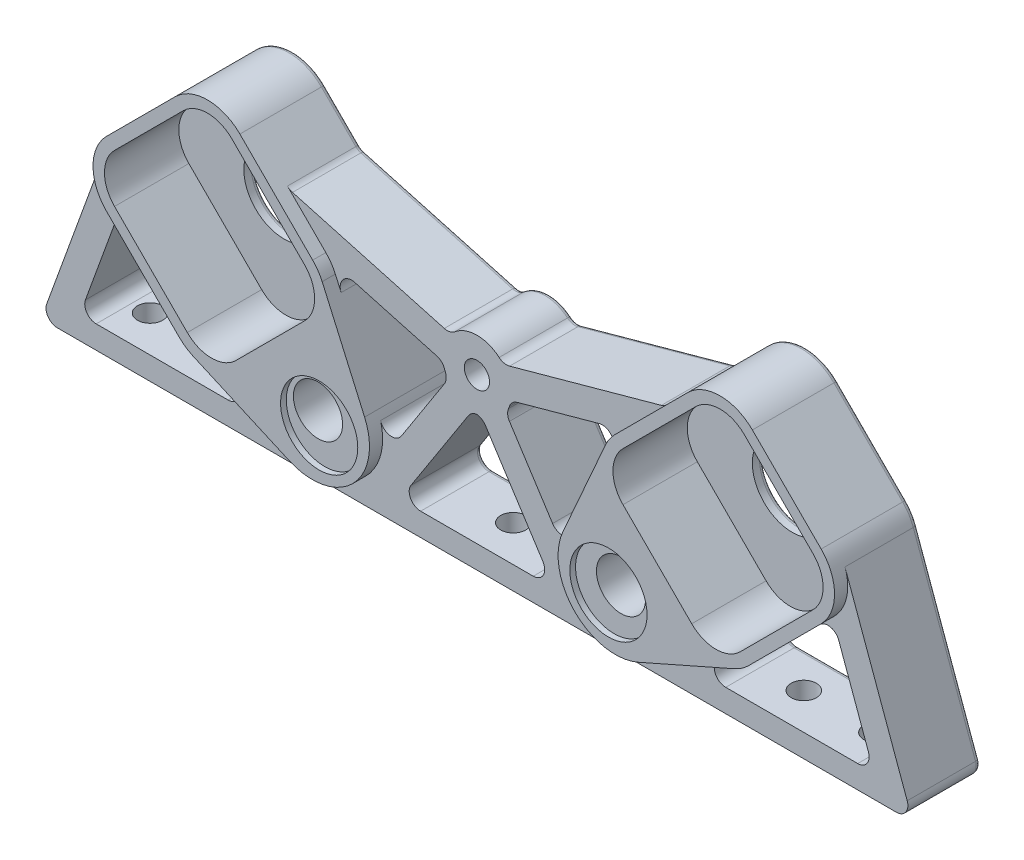
SolidWorks part; units mm, degrees
ref_plane "Front Plane" through (0, 0, 0) normal (0, 0, 1) x (1, 0, 0)
ref_plane "Top Plane" through (0, 0, 0) normal (0, 1, 0) x (1, 0, 0)
ref_plane "Right Plane" through (0, 0, 0) normal (1, 0, 0) x (0, 0, -1)
sketch "Sketch1" plane through (0, 0, 0) normal (0, 0, 1) x (1, 0, 0)
  line L0 (0, 0) -> (60.4965, 0) construction
  circle A0 centre (0, 0) radius 25.4 construction
  circle A1 centre (44.45, 35.921) radius 31.75 construction
  circle A2 centre (133.35, 35.921) radius 31.75 construction
  circle A3 centre (177.8, 0) radius 25.4 construction
  circle A4 centre (222.25, 35.921) radius 31.75 construction
  circle A5 centre (311.15, 35.921) radius 31.75 construction
  circle A6 centre (355.6, 0) radius 25.4 construction
  circle A7 centre (0, 0) radius 50.8 construction
  circle A8 centre (355.6, 0) radius 50.8 construction
  circle A9 centre (177.8, 0) radius 50.8 construction
  circle A10 centre (88.9, 35.921) radius 12.7 construction
  circle A11 centre (266.7, 35.921) radius 12.7 construction
  point P20 (-50.8, 0)
  point P21 (406.4, 0)
  dimension "D1" = 50.8
  dimension "D2" = 63.5
  dimension "D4" = 101.6
  dimension "D5" = 25.4
  dimension "D6" = 25.4
  dimension "D3" = 355.6
  dimension "D7" = 177.8
  dimension "D8" = 177.8
  dimension "D9" = 457.2
  dimension "D10" = 44.45
sketch "Sketch2" plane through (0, 0, 0) normal (0, 0, 1) x (1, 0, 0)
  line L0 (-200000, 0) -> (200060.4965, 0) construction
  line L1 (-44.45, 6.35) -> (400.05, 6.35) construction
  line L2 (-44.45, 6.35) -> (-44.45, -19.05) construction
  line L3 (-44.45, -19.05) -> (400.05, -19.05) construction
  line L4 (400.05, 6.35) -> (400.05, -19.05) construction
  circle A0 centre (-38.1, 0) radius 2.25 construction
  circle A2 centre (-31.75, -6.35) radius 2.25 construction
  circle A3 centre (-25.4, 0) radius 2.25 construction
  circle A4 centre (-12.7, 0) radius 2.25 construction
  circle A5 centre (0, 0) radius 2.25 construction
  circle A6 centre (12.7, 0) radius 2.25 construction
  circle A7 centre (25.4, 0) radius 2.25 construction
  circle A8 centre (38.1, 0) radius 2.25 construction
  circle A9 centre (50.8, 0) radius 2.25 construction
  circle A10 centre (63.5, 0) radius 2.25 construction
  circle A11 centre (76.2, 0) radius 2.25 construction
  circle A12 centre (88.9, 0) radius 2.25 construction
  circle A13 centre (101.6, 0) radius 2.25 construction
  circle A14 centre (114.3, 0) radius 2.25 construction
  circle A15 centre (127, 0) radius 2.25 construction
  circle A16 centre (139.7, 0) radius 2.25 construction
  circle A17 centre (152.4, 0) radius 2.25 construction
  circle A18 centre (165.1, 0) radius 2.25 construction
  circle A19 centre (177.8, 0) radius 2.25 construction
  circle A20 centre (190.5, 0) radius 2.25 construction
  circle A21 centre (203.2, 0) radius 2.25 construction
  circle A22 centre (215.9, 0) radius 2.25 construction
  circle A23 centre (228.6, 0) radius 2.25 construction
  circle A24 centre (241.3, 0) radius 2.25 construction
  circle A25 centre (254, 0) radius 2.25 construction
  circle A26 centre (266.7, 0) radius 2.25 construction
  circle A27 centre (279.4, 0) radius 2.25 construction
  circle A28 centre (292.1, 0) radius 2.25 construction
  circle A29 centre (304.8, 0) radius 2.25 construction
  circle A30 centre (317.5, 0) radius 2.25 construction
  circle A31 centre (330.2, 0) radius 2.25 construction
  circle A32 centre (342.9, 0) radius 2.25 construction
  circle A33 centre (355.6, 0) radius 2.25 construction
  circle A34 centre (368.3, 0) radius 2.25 construction
  circle A35 centre (381, 0) radius 2.25 construction
  circle A36 centre (393.7, 0) radius 2.25 construction
  circle A37 centre (-25.4, -12.7) radius 2.25 construction
  circle A38 centre (-12.7, -12.7) radius 2.25 construction
  circle A39 centre (0, -12.7) radius 2.25 construction
  circle A40 centre (12.7, -12.7) radius 2.25 construction
  circle A41 centre (25.4, -12.7) radius 2.25 construction
  circle A42 centre (38.1, -12.7) radius 2.25 construction
  circle A43 centre (50.8, -12.7) radius 2.25 construction
  circle A44 centre (63.5, -12.7) radius 2.25 construction
  circle A45 centre (76.2, -12.7) radius 2.25 construction
  circle A46 centre (88.9, -12.7) radius 2.25 construction
  circle A47 centre (101.6, -12.7) radius 2.25 construction
  circle A48 centre (114.3, -12.7) radius 2.25 construction
  circle A49 centre (127, -12.7) radius 2.25 construction
  circle A50 centre (139.7, -12.7) radius 2.25 construction
  circle A51 centre (152.4, -12.7) radius 2.25 construction
  circle A52 centre (165.1, -12.7) radius 2.25 construction
  circle A53 centre (177.8, -12.7) radius 2.25 construction
  circle A54 centre (190.5, -12.7) radius 2.25 construction
  circle A55 centre (203.2, -12.7) radius 2.25 construction
  circle A56 centre (215.9, -12.7) radius 2.25 construction
  circle A57 centre (228.6, -12.7) radius 2.25 construction
  circle A58 centre (241.3, -12.7) radius 2.25 construction
  circle A59 centre (254, -12.7) radius 2.25 construction
  circle A60 centre (266.7, -12.7) radius 2.25 construction
  circle A61 centre (279.4, -12.7) radius 2.25 construction
  circle A62 centre (292.1, -12.7) radius 2.25 construction
  circle A63 centre (304.8, -12.7) radius 2.25 construction
  circle A64 centre (317.5, -12.7) radius 2.25 construction
  circle A65 centre (330.2, -12.7) radius 2.25 construction
  circle A66 centre (342.9, -12.7) radius 2.25 construction
  circle A67 centre (355.6, -12.7) radius 2.25 construction
  circle A68 centre (368.3, -12.7) radius 2.25 construction
  circle A69 centre (381, -12.7) radius 2.25 construction
  circle A70 centre (393.7, -12.7) radius 2.25 construction
  circle A71 centre (-38.1, -12.7) radius 2.25 construction
  circle A72 centre (-19.05, -6.35) radius 2.25 construction
  circle A73 centre (-6.35, -6.35) radius 2.25 construction
  circle A74 centre (6.35, -6.35) radius 2.25 construction
  circle A75 centre (19.05, -6.35) radius 2.25 construction
  circle A76 centre (31.75, -6.35) radius 2.25 construction
  circle A77 centre (44.45, -6.35) radius 2.25 construction
  circle A78 centre (57.15, -6.35) radius 2.25 construction
  circle A79 centre (69.85, -6.35) radius 2.25 construction
  circle A80 centre (82.55, -6.35) radius 2.25 construction
  circle A81 centre (95.25, -6.35) radius 2.25 construction
  circle A82 centre (107.95, -6.35) radius 2.25 construction
  circle A83 centre (120.65, -6.35) radius 2.25 construction
  circle A84 centre (133.35, -6.35) radius 2.25 construction
  circle A85 centre (146.05, -6.35) radius 2.25 construction
  circle A86 centre (158.75, -6.35) radius 2.25 construction
  circle A87 centre (171.45, -6.35) radius 2.25 construction
  circle A88 centre (184.15, -6.35) radius 2.25 construction
  circle A89 centre (196.85, -6.35) radius 2.25 construction
  circle A90 centre (209.55, -6.35) radius 2.25 construction
  circle A91 centre (222.25, -6.35) radius 2.25 construction
  circle A92 centre (234.95, -6.35) radius 2.25 construction
  circle A93 centre (247.65, -6.35) radius 2.25 construction
  circle A94 centre (260.35, -6.35) radius 2.25 construction
  circle A95 centre (273.05, -6.35) radius 2.25 construction
  circle A96 centre (285.75, -6.35) radius 2.25 construction
  circle A97 centre (298.45, -6.35) radius 2.25 construction
  circle A98 centre (311.15, -6.35) radius 2.25 construction
  circle A99 centre (323.85, -6.35) radius 2.25 construction
  circle A100 centre (336.55, -6.35) radius 2.25 construction
  circle A101 centre (349.25, -6.35) radius 2.25 construction
  circle A102 centre (361.95, -6.35) radius 2.25 construction
  circle A103 centre (374.65, -6.35) radius 2.25 construction
  circle A104 centre (387.35, -6.35) radius 2.25 construction
  point P4 (0, 0)
  point P7 (0, 0)
  dimension "D5" = 4.5
  dimension "D1" = 25.4
  dimension "D2" = 444.5
  dimension "D3" = 6.35
  dimension "D4" = 44.45
  dimension "D6" = 6.35
  dimension "D7" = 6.35
  dimension "D8" = 6.35
  dimension "D12" = 12.7
  dimension "D9" = 35
  dimension "D10" = 2
  dimension "D11" = 34
sketch "Sketch4" plane through (0, 0, 0) normal (0, 0, 1) x (1, 0, 0)
  line L0 (61.067, 39.8101) -> (48.3391, 52.538)
  line L1 (61.067, 31.3248) -> (49.0462, 19.304)
  line L2 (39.8538, 52.538) -> (27.833, 40.5172)
  line L3 (40.5609, 19.304) -> (27.833, 32.0319)
  line L4 (65.3097, 35.5675) -> (23.5903, 36.2746) construction
  line L5 (44.0964, 56.7807) -> (44.8036, 15.0614) construction
  line L6 (44.9803, 59.0788) -> (21.2923, 35.3907) construction
  line L7 (44.45, 35.921) -> (62.4105, 17.9605) construction
  line L8 (62.4105, 17.9605) -> (63.6126, 16.7584) construction
  line L9 (33.1363, 47.2347) -> (74.1485, 6.2225) construction
  line L10 (88.9, 35.921) -> (88.9, 9.7206) construction
  line L11 (44.9803, 59.0788) -> (85.9925, 18.0666) construction
  line L12 (21.2923, 35.3907) -> (62.3044, -5.6215) construction
  line L13 (85.9925, 18.0666) -> (62.3044, -5.6215) construction
  line L14 (132.8197, 59.0788) -> (156.5077, 35.3907) construction
  line L15 (156.5077, 35.3907) -> (115.4956, -5.6215) construction
  line L16 (132.8197, 59.0788) -> (91.8075, 18.0666) construction
  line L17 (91.8075, 18.0666) -> (115.4956, -5.6215) construction
  line L18 (137.9462, 52.538) -> (149.967, 40.5172)
  line L19 (137.2391, 19.304) -> (149.967, 32.0319)
  line L20 (116.733, 31.3248) -> (128.7538, 19.304)
  line L21 (116.733, 39.8101) -> (129.4609, 52.538)
  line L25 (-44.45, 6.35) -> (400.05, 6.35) construction
  circle A0 centre (44.45, 35.921) radius 7
  circle A1 centre (88.9, 35.921) radius 2.2
  arc A3 (61.067, 39.8101) -> (61.067, 31.3248) centre (56.8244, 35.5675) cw
  circle A4 centre (62.4105, 17.9605) radius 4.3
  circle A5 centre (63.6126, 16.7584) radius 6.75
  arc A6 (49.0462, 19.304) -> (40.5609, 19.304) centre (44.8036, 23.5467) cw
  arc A7 (27.833, 32.0319) -> (27.833, 40.5172) centre (32.0756, 36.2746) cw
  arc A8 (39.8538, 52.538) -> (48.3391, 52.538) centre (44.0964, 48.2954) cw
  circle A9 centre (115.3895, 17.9605) radius 4.3
  circle A10 centre (114.1874, 16.7584) radius 6.75
  circle A11 centre (133.35, 35.921) radius 7
  arc A12 (149.967, 32.0319) -> (149.967, 40.5172) centre (145.7244, 36.2746) ccw
  arc A13 (128.7538, 19.304) -> (137.2391, 19.304) centre (132.9964, 23.5467) ccw
  arc A14 (116.733, 39.8101) -> (116.733, 31.3248) centre (120.9756, 35.5675) ccw
  arc A15 (137.9462, 52.538) -> (129.4609, 52.538) centre (133.7036, 48.2954) ccw
  dimension "D1" = 4.4
  dimension "D2" = 14
  dimension "D7" = 13.5
  dimension "D8" = 8.6
  dimension "D9" = 6
  dimension "D3" = 29
  dimension "D4" = 30
  dimension "D5" = 10.4
  dimension "D6" = 1.7
  dimension "D10" = 58
  dimension "D11" = 33.5
  dimension "D12" = 16
  dimension "D13" = 45
sketch "Sketch6" plane through (0, 0, 0) normal (0, 0, 1) x (1, 0, 0)
  line L0 (72.4105, 10.35) -> (105.3895, 10.35)
  line L1 (88.9, 200035.921) -> (88.9, -199990.2794) construction
  line L2 (165.1, 6.35) -> (12.7, 6.35)
  line L3 (-44.45, 6.35) -> (400.05, 6.35) construction
  line L8 (40.5609, 19.304) -> (27.833, 32.0319) construction
  line L9 (61.067, 31.3248) -> (49.0462, 19.304) construction
  line L10 (61.067, 39.8101) -> (48.3391, 52.538) construction
  line L11 (39.8538, 52.538) -> (27.833, 40.5172) construction
  line L12 (40.5609, 19.304) -> (27.833, 32.0319) construction
  line L13 (61.067, 31.3248) -> (49.0462, 19.304) construction
  line L14 (61.067, 39.8101) -> (48.3391, 52.538) construction
  line L15 (62.4812, 41.2243) -> (49.7533, 53.9522)
  line L16 (39.8538, 52.538) -> (27.833, 40.5172) construction
  line L18 (38.4396, 53.9522) -> (26.4188, 41.9314)
  line L21 (39.1467, 17.8898) -> (26.4188, 30.6177)
  line L22 (71.5588, 21.9989) -> (64.143, 38.7982)
  line L23 (41.5728, 16.228) -> (58.3721, 8.8122)
  line L24 (54.8885, 10.35) -> (19.4716, 10.35)
  line L34 (19.4716, 10.35) -> (26.7206, 30.3159)
  line L37 (88.9, 35.921) -> (105.3895, 10.35) construction
  line L38 (12.7, 6.35) -> (24.5559, 39.0048)
  line L39 (88.9, 35.921) -> (44.0964, 48.2954) construction
  line L40 (84.308, 39.7829) -> (56.144, 47.5616)
  line L41 (63.1751, 40.4324) -> (82.9769, 34.9633)
  line L42 (88.9, 35.921) -> (133.7036, 48.2954) construction
  line L43 (137.9462, 52.538) -> (149.967, 40.5172) construction
  line L44 (88.9, 35.921) -> (72.4105, 10.35) construction
  line L45 (116.733, 39.8101) -> (129.4609, 52.538) construction
  line L46 (72.4105, 17.9605) -> (72.4105, 10.35)
  line L47 (72.4105, 14.963) -> (83.843, 32.692)
  line L48 (75.3852, 10.35) -> (88.0451, 29.9822)
  line L49 (116.733, 31.3248) -> (128.7538, 19.304) construction
  line L50 (88.9, 35.921) -> (88.9, 10.35) construction
  line L51 (137.2391, 19.304) -> (149.967, 32.0319) construction
  line L52 (102.4148, 10.35) -> (89.7549, 29.9822)
  line L53 (105.3895, 14.963) -> (93.957, 32.692)
  line L54 (105.3895, 17.9605) -> (105.3895, 10.35)
  line L55 (114.6249, 40.4324) -> (94.8231, 34.9633)
  line L56 (93.492, 39.7829) -> (121.656, 47.5616)
  line L57 (165.1, 6.35) -> (153.2441, 39.0048)
  line L58 (158.3284, 10.35) -> (151.0794, 30.3159)
  line L59 (122.9115, 10.35) -> (158.3284, 10.35)
  line L60 (136.2272, 16.228) -> (119.4279, 8.8122)
  line L61 (106.2412, 21.9989) -> (113.657, 38.7982)
  line L62 (138.6533, 17.8898) -> (151.3812, 30.6177)
  line L63 (139.3604, 53.9522) -> (151.3812, 41.9314)
  line L64 (115.3188, 41.2243) -> (128.0467, 53.9522)
  arc A0 (62.4812, 29.9106) -> (62.4812, 41.2243) centre (56.8244, 35.5675) ccw
  arc A1 (39.1467, 17.8898) -> (50.4604, 17.8898) centre (44.8036, 23.5467) ccw
  arc A2 (149.967, 40.5172) -> (149.967, 32.0319) centre (145.7244, 36.2746) cw construction
  arc A3 (129.4609, 52.538) -> (137.9462, 52.538) centre (133.7036, 48.2954) cw construction
  arc A4 (116.733, 31.3248) -> (116.733, 39.8101) centre (120.9756, 35.5675) cw construction
  arc A5 (137.2391, 19.304) -> (128.7538, 19.304) centre (132.9964, 23.5467) cw construction
  arc A12 (40.5609, 19.304) -> (49.0462, 19.304) centre (44.8036, 23.5467) ccw construction
  arc A14 (61.067, 31.3248) -> (61.067, 39.8101) centre (56.8244, 35.5675) ccw construction
  arc A15 (48.3391, 52.538) -> (39.8538, 52.538) centre (44.0964, 48.2954) ccw construction
  arc A16 (27.833, 40.5172) -> (27.833, 32.0319) centre (32.0756, 36.2746) ccw construction
  arc A17 (40.5609, 19.304) -> (49.0462, 19.304) centre (44.8036, 23.5467) ccw construction
  arc A18 (61.067, 31.3248) -> (61.067, 39.8101) centre (56.8244, 35.5675) ccw construction
  arc A19 (48.3391, 52.538) -> (39.8538, 52.538) centre (44.0964, 48.2954) ccw construction
  arc A20 (27.833, 40.5172) -> (27.833, 32.0319) centre (32.0756, 36.2746) ccw construction
  arc A21 (26.4188, 41.9314) -> (26.4188, 30.6177) centre (32.0756, 36.2746) ccw
  arc A22 (49.7533, 53.9522) -> (38.4396, 53.9522) centre (44.0964, 48.2954) ccw
  circle A25 centre (62.4105, 17.9605) radius 4.3 construction
  circle A26 centre (62.4105, 17.9605) radius 4.3
  circle A27 centre (115.3895, 17.9605) radius 10
  circle A28 centre (115.3895, 17.9605) radius 4.3
  arc A29 (128.0467, 53.9522) -> (139.3604, 53.9522) centre (133.7036, 48.2954) cw
  arc A30 (151.3812, 41.9314) -> (151.3812, 30.6177) centre (145.7244, 36.2746) cw
  arc A41 (138.6533, 17.8898) -> (127.3396, 17.8898) centre (132.9964, 23.5467) cw
  arc A42 (115.3188, 29.9106) -> (115.3188, 41.2243) centre (120.9756, 35.5675) cw
  circle A43 centre (62.4105, 17.9605) radius 10
  circle A44 centre (88.9, 35.921) radius 6
  point P3 (15.6601, 6.35)
  point P19 (0, 0)
  point P20 (0, 0)
  point P48 (0, 0)
  point P49 (0, 0)
  point P50 (0, 0)
  point P62 (88.9, 10.35)
  point P86 (88.9, 6.35)
  dimension "D4" = 12
  dimension "D6" = 4
  dimension "D2" = 2
  dimension "D3" = 20
  dimension "D7" = 5
  dimension "D12" = 8
  dimension "D13" = 8
  dimension "D5" = 2
  dimension "D8" = 5
  dimension "D9" = 2.5
  dimension "D10" = 5
  dimension "D11" = 2.5
  dimension "D14" = 2
  dimension "D15" = 17
extrude "Boss-Extrude1" add sketch "Sketch6" along normal blind 12.7 contours A43 L22 A0 L15 A22 L18 A21 L21 A1 L23 | A43 L23 L24 L34 L21 A21 L38 L2 L57 A30 L62 L58 L59 L60 A27 L54 L0 L46 | A43 A26 | A44 L47 L46 L0 L48 | A44 L40 L15 A0 L41 | A44 | A44 L55 A42 L64 L56 | A44 L52 L0 L54 L53 | A27 A28 | A42 L61 A27 L60 A41 L62 A30 L63 A29 L64 region at (79.4718, 21.2253, 0) region at (73.8979, 8.7914, 0) region at (98.3282, 21.2253, 0) region at (88.9, 35.921, 0) region at (67.7158, 9.8194, 0) region at (45.2363, 35.1347, 0) region at (71.4188, 40.9045, 0) region at (105.8815, 19.9658, 0) region at (106.3812, 40.9045, 0) region at (132.5637, 35.1347, 0)
extrude "Boss-Extrude2" add sketch "Sketch6<3>" along normal blind 15 contours A42 L61 A27 L60 A41 L62 A30 L63 A29 L64 | A27 A28 | A43 A26 | A43 L22 A0 L15 A22 L18 A21 L21 A1 L23 region at (67.7158, 9.8194, 0) region at (45.2363, 35.1347, 0) region at (105.8815, 19.9658, 0) region at (132.5637, 35.1347, 0)
sketch "Sketch6<3>" plane through (0, 0, 0) normal (0, 0, 1) x (1, 0, 0) same geometry as "Sketch6"
extrude "Cut-Extrude1" cut sketch "Sketch4" against normal blind 13 from surface contours L18 A15 L21 A14 L20 A13 L19 A12 A11 | A8 L2 A7 L3 A6 L1 A3 L0 A0 region at (62.3047, 35.5675, 0) region at (143.5891, 46.1601, 0) starting at face at (129.7486, 32.3197, 15)
extrude "Cut-Extrude2" cut sketch "Sketch4<4>" along normal up to next contours A0 | A1 | A11 region at (44.45, 35.921, 0) region at (88.9, 35.921, 0) region at (133.35, 35.921, 0)
sketch "Sketch4<4>" plane through (0, 0, 0) normal (0, 0, 1) x (1, 0, 0) same geometry as "Sketch4"
extrude "Cut-Extrude3" cut sketch "Sketch4<5>" against normal blind 1 from surface contours A5 A4 | A10 A9 region at (57.0535, 16.7584, 0) region at (107.6283, 16.7584, 0) starting at face at (48.0514, 32.3197, 15)
sketch "Sketch4<5>" plane through (0, 0, 0) normal (0, 0, 1) x (1, 0, 0) same geometry as "Sketch4"
fillet "Fillet1" radius 2 24 edges at (56.144, 47.5616, 6.35) (121.656, 47.5616, 6.35) (93.492, 39.7829, 6.35) (84.308, 39.7829, 6.35) (165.1, 6.35, 6.35) (151.0794, 30.3159, 6.35) (158.3284, 10.35, 6.35) (122.9115, 10.35, 6.35) (114.6249, 40.4324, 6.35) (93.957, 32.692, 6.35) (94.8231, 34.9633, 6.35) (105.3895, 14.963, 6.35) (102.4148, 10.35, 6.35) (89.7549, 29.9822, 6.35) (88.0451, 29.9822, 6.35) (75.3852, 10.35, 6.35) (72.4105, 14.963, 6.35) (83.843, 32.692, 6.35) (82.9769, 34.9633, 6.35) (63.1751, 40.4324, 6.35) (12.7, 6.35, 6.35) (26.7206, 30.3159, 6.35) (19.4716, 10.35, 6.35) (54.8885, 10.35, 6.35)
sketch "Sketch7" plane through (0, 6.35, 0) normal (0, -1, 0) x (1, 0, 0)
  line L0 (15.5539, 12.7) -> (15.5539, 0) construction
  circle A0 centre (25.4, 6.35) radius 2.2
  circle A1 centre (38.1, 6.35) radius 2.2
  circle A2 centre (88.9, 6.35) radius 2.2
  circle A3 centre (139.7, 6.35) radius 2.2
  circle A4 centre (152.4, 6.35) radius 2.2
  point P0 (152.4, 0)
  point P2 (139.7, 0)
  point P4 (88.9, 0)
  point P6 (38.1, 0)
  point P8 (25.4, 0)
  point P20 (0, 0)
  point P23 (0, 0)
  point P24 (15.5539, 6.35)
  point P25 (0, 0)
  point P26 (0, 0)
  point P27 (0, 0)
  point P28 (0, 0)
  point P29 (0, 0)
  dimension "D1" = 4.4
extrude "Cut-Extrude4" cut sketch "Sketch7" against normal up to next
fillet "Fillet2" radius 0.75 66 edges at (51.45, 35.921, 0) (91.1, 35.921, 0) (105.9633, 21.2993, 0) (104.1152, 19.1284, 0) (98.3568, 25.869, 0) (94.2739, 32.629, 0) (94.5063, 33.7833, 0) (95.1014, 34.7993, 0) (103.1101, 37.2521, 0) (112.3251, 38.6114, 0) (109.4411, 29.2477, 0) (137.5172, 16.9465, 0) (143.7554, 22.9919, 0) (150.7054, 28.6323, 0) (154.7531, 20.1975, 0) (157.1123, 11.2022, 0) (143.9346, 10.35, 0) (130.4377, 11.9373, 0) (133.9071, 15.2038, 0) (88.0546, 29.6302, 0) (89.7454, 29.6302, 0) (95.4048, 21.2206, 0) (100.5014, 11.3929, 0) (88.9, 10.35, 0) (77.2986, 11.3929, 0) (82.3952, 21.2206, 0) (119.6895, 17.9605, 0) (66.7105, 17.9605, 0) (40.2828, 16.9465, 0) (43.8929, 15.2038, 0) (47.3623, 11.9373, 0) (33.8654, 10.35, 0) (20.6877, 11.2022, 0) (23.0469, 20.1975, 0) (27.0946, 28.6323, 0) (34.0446, 22.9919, 0) (152.4732, 40.5703, 0) (145.3708, 47.9418, 0) (133.7036, 56.2954, 0) (125.0379, 50.9435, 0) (121.6216, 47.6207, 0) (107.8787, 43.7564, 0) (93.6466, 40.0665, 0) (88.9, 41.921, 0) (84.1534, 40.0665, 0) (69.9213, 43.7564, 0) (56.1784, 47.6207, 0) (52.7621, 50.9435, 0) (44.0964, 56.2954, 0) (32.4292, 47.9418, 0) (25.3268, 40.5703, 0) (19.1149, 24.0186, 0) (13.916, 7.2022, 0) (88.9, 6.35, 0) (163.884, 7.2022, 0) (158.6851, 24.0186, 0) (82.6986, 34.7993, 0) (83.2937, 33.7833, 0) (83.5261, 32.629, 0) (79.4432, 25.869, 0) (73.6848, 19.1284, 0) (71.8367, 21.2993, 0) (68.3589, 29.2477, 0) (65.4749, 38.6114, 0) (74.6899, 37.2521, 0) (140.35, 35.921, 0)
